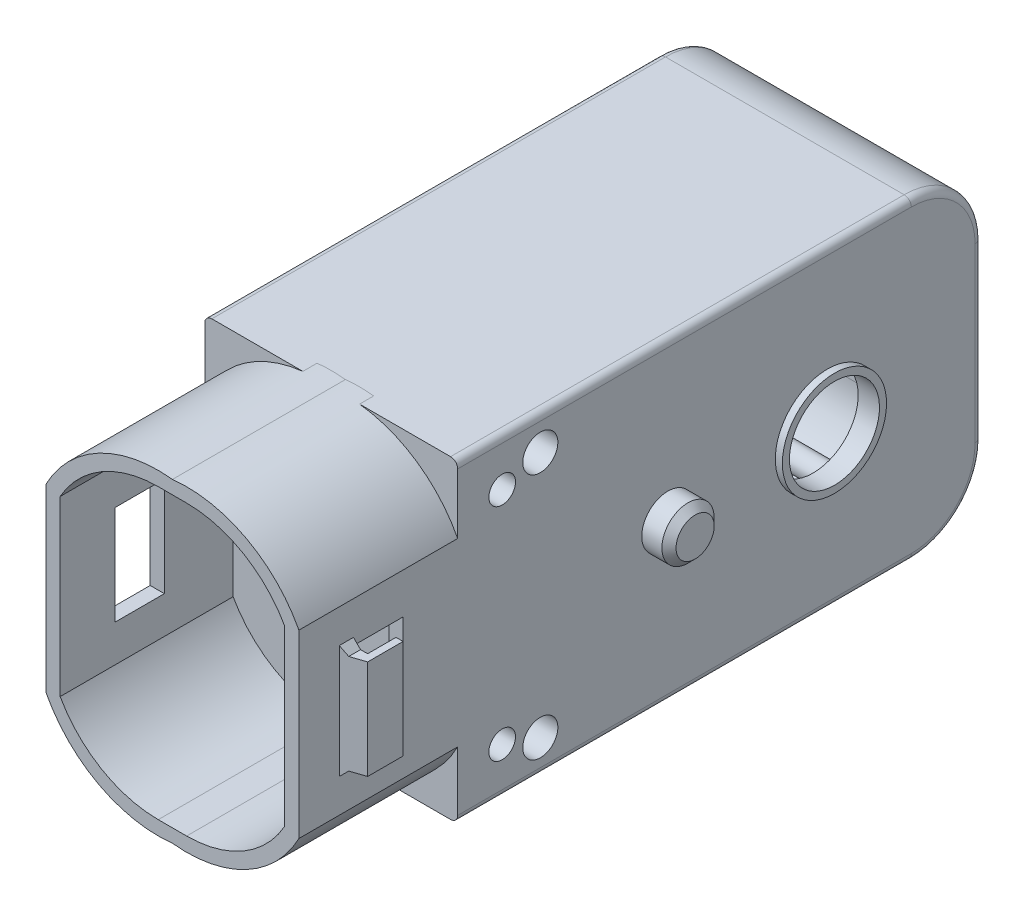
SolidWorks part; units mm, degrees
ref_plane "Front Plane" through (0, 0, 0) normal (0, 0, 1) x (1, 0, 0)
ref_plane "Top Plane" through (0, 0, 0) normal (0, 1, 0) x (1, 0, 0)
ref_plane "Right Plane" through (0, 0, 0) normal (1, 0, 0) x (0, 0, -1)
sketch "Sketch1" plane through (0, 0, 0) normal (0, 0, 1) x (1, 0, 0)
  line L0 (0, 11.115) -> (0, 10.1712)
  line L2 (-8.92, 6.365) -> (-8.92, -6.365)
  line L4 (-8.92, 6.365) -> (-8.92, -6.365) construction
  line L5 (55, 0) -> (-55, 0) construction
  line L7 (-7.92, 6.1126) -> (-7.92, -6.1126)
  line L8 (-1, 10.1712) -> (-1, -10.1712) construction
  line L9 (-1, 10.1712) -> (0, 10.1712)
  line L10 (-1, -10.1712) -> (0, -10.1712)
  line L11 (0, -10.1712) -> (0, -11.115)
  line L13 (0, 11.115) -> (0, -11.115) construction
  arc A0 (-8.92, 6.365) -> (0, 11.115) centre (-1, 2.2425) cw
  arc A1 (-8.92, -6.365) -> (0, -11.115) centre (-1, -2.2425) ccw
  arc A2 (-7.92, -6.1126) -> (-1, -10.1712) centre (-1, -2.2425) ccw
  arc A3 (-7.92, 6.1126) -> (-1, 10.1712) centre (-1, 2.2425) cw
  dimension "D1" = 22.23
  dimension "D2" = 12.73
  dimension "D3" = 1
extrude "Boss-Extrude1" add sketch "Sketch1" along normal blind 11.2
sketch "Sketch2" plane through (0, 0, 0) normal (0, 0, -1) x (-1, 0, 0)
  line L0 (0, -10.1712) -> (1, -10.1712) construction
  line L1 (2, 11.115) -> (8.92, 11.115)
  line L2 (0, 11.115) -> (0, 10.1712)
  line L3 (2.4484, -11.0529) -> (8.92, -11.0529)
  line L4 (8.92, 11.115) -> (8.92, -11.0529)
  line L5 (7.92, -6.1126) -> (7.92, 6.1126) construction
  line L6 (1, 10.1712) -> (0, 10.1712) construction
  line L7 (0, -10.1712) -> (1, -10.1712)
  line L8 (7.92, -6.1126) -> (7.92, 6.1126)
  line L9 (1, 10.1712) -> (0, 10.1712)
  line L10 (0, -10.1712) -> (0, -11.115)
  line L11 (8.92, 6.365) -> (8.92, -6.365) construction
  arc A0 (8.92, 6.365) -> (0, 11.115) centre (1, 2.2425) ccw construction
  arc A1 (2, 11.115) -> (0, 11.115) centre (1, 2.2425) ccw
  arc A2 (0, -11.115) -> (8.92, -6.365) centre (1, -2.2425) ccw construction
  arc A3 (0, -11.115) -> (2.4484, -11.0529) centre (1, -2.2425) ccw
  arc A4 (1, -10.1712) -> (7.92, -6.1126) centre (1, -2.2425) ccw construction
  arc A5 (7.92, 6.1126) -> (1, 10.1712) centre (1, 2.2425) ccw construction
  arc A6 (1, -10.1712) -> (7.92, -6.1126) centre (1, -2.2425) ccw
  arc A7 (7.92, 6.1126) -> (1, 10.1712) centre (1, 2.2425) ccw
extrude "Boss-Extrude2" add sketch "Sketch2" along normal blind 1
sketch "Sketch4" plane through (0, 0, -1) normal (0, 0, -1) x (-1, 0, 0)
  line L0 (0, -10.1712) -> (0, -11.115) construction
  line L1 (8.92, 11.115) -> (0, 11.115)
  line L2 (8.92, 11.115) -> (8.92, -11.0529)
  line L3 (8.92, -11.0529) -> (0, -11.0529)
  line L4 (0, 11.115) -> (0, 10.115)
  line L5 (2.4484, -11.0529) -> (8.92, -11.0529) construction
  line L6 (7.92, 10.115) -> (7.92, -10.0529)
  line L7 (7.92, -10.0529) -> (1, -10.0529)
  line L9 (7.92, 10.115) -> (1, 10.115)
  line L10 (1, 10.115) -> (0, 10.115)
  line L11 (1, -10.0529) -> (0, -10.0529)
  line L12 (0, -10.0529) -> (0, -11.0529)
  line L13 (1, 10.115) -> (1, -10.0529) construction
  line L15 (0, 11.115) -> (0, -11.0529) construction
  dimension "D1" = 1
extrude "Boss-Extrude4" add sketch "Sketch4" along normal blind 36
sketch "Sketch5" plane through (0, 0, -37) normal (0, 0, -1) x (-1, 0, 0)
  line L1 (0, 11.115) -> (8.92, 11.115)
  line L2 (0, 11.115) -> (0, -11.0529)
  line L3 (0, -11.0529) -> (8.92, -11.0529)
  line L4 (8.92, 11.115) -> (8.92, -11.0529)
extrude "Boss-Extrude6" add sketch "Sketch5" against normal blind 2
fillet "Fillet2" radius 5 4 edges at (-3.96, -10.0529, -35) (-3.96, 10.115, -35) (-4.46, -11.0529, -37) (-4.46, 11.115, -37)
sketch "Sketch6" plane through (0, 0, -37) normal (0, 0, -1) x (-1, 0, 0)
  line L0 (0, 0) -> (1.4, 0) construction
  line L1 (0, 6.115) -> (0, -6.0529) construction
  line L2 (1.4, -2.5) -> (0, -2.5)
  line L3 (1.4, -2.5) -> (1.4, 2.5)
  line L4 (1.4, 2.5) -> (0, 2.5)
  line L5 (0, -2.5) -> (0, 2.5)
  line L6 (1.4, -2.5) -> (0, 2.5) construction
  line L7 (1.4, 2.5) -> (0, -2.5) construction
  point P3 (0.7, 0)
  dimension "D1" = 1.4
  dimension "D2" = 5
extrude "Boss-Extrude7" add sketch "Sketch6" along normal blind 4.8
sketch "Sketch7" plane through (-1.4, 0, 0) normal (-1, 0, 0) x (0, 0, 1)
  line L0 (-39.4, 2.5) -> (-39.4, -2.5) construction
  line L1 (-41.8, 2.5) -> (-37, 2.5) construction
  line L2 (-41.8, -2.5) -> (-37, -2.5) construction
  line L3 (-37, -2.5) -> (-37, 2.5) construction
  circle A0 centre (-39.4, 0) radius 1.38
  dimension "D1" = 2.76
extrude "Cut-Extrude1" cut sketch "Sketch7" against normal blind 4.8
sketch "Sketch8" plane through (-8.92, 0, 0) normal (-1, 0, 0) x (0, 0, 1)
  line L0 (-37, 0) -> (-26.08, 0) construction
  line L1 (-37, -2.5) -> (-37, 2.5) construction
  circle A0 centre (-26.08, 0) radius 3.675
  circle A2 centre (-26.08, 0) radius 3.175
  dimension "D2" = 7.35
  dimension "D3" = 0.5
  dimension "D1" = 10.92
extrude "Boss-Extrude8" add sketch "Sketch8" along normal blind 0.5
sketch "Sketch9" plane through (-8.92, 0, 0) normal (-1, 0, 0) x (0, 0, 1)
  circle A1 centre (-26.08, 0) radius 3.175
  circle A2 centre (-26.08, 0) radius 3.175
  dimension "D1" = 0
extrude "Cut-Extrude2" cut sketch "Sketch9" against normal blind 7.5
chamfer "Chamfer1" distance 1 angle 45 2 edges at (-0.7, -2.5, -37) (-0.7, 2.5, -37)
sketch "Sketch10" plane through (-8.92, 0, 0) normal (-1, 0, 0) x (0, 0, 1)
  line L0 (-26.08, 0) -> (-14.83, 0) construction
  circle A0 centre (-14.83, 0) radius 1.845
  dimension "D2" = 3.69
  dimension "D1" = 11.25
extrude "Boss-Extrude9" add sketch "Sketch10" along normal blind 1.92
chamfer "Chamfer2" distance 0.5 angle 45 1 edges at (-10.84, 0, -12.985)
sketch "Sketch11" plane through (-8.92, 0, 0) normal (-1, 0, 0) x (0, 0, 1)
  line L0 (-14.83, 0) -> (-5.83, 0) construction
  line L1 (-5.83, 8.71) -> (-5.83, -8.71) construction
  line L2 (-37, -6.0529) -> (-37, 6.115) construction
  circle A0 centre (-5.83, 8.71) radius 1.5
  circle A1 centre (-5.83, -8.71) radius 1.5
  dimension "D4" = 3
  dimension "D1" = 31.17
  dimension "D2" = 17.42
extrude "Cut-Extrude3" cut sketch "Sketch11" against normal blind 1.92
sketch "Sketch12" plane through (-8.92, 0, 0) normal (-1, 0, 0) x (0, 0, 1)
  line L0 (4.906, 0) -> (-4.906, 0) construction
  circle A0 centre (-3.14, 7.7815) radius 1.15
  circle A1 centre (-3.14, -7.7815) radius 1.15
  dimension "D1" = 2.3
extrude "Cut-Extrude4" cut sketch "Sketch12" against normal blind 1.92
ref_plane "Plane1" through (0, 0, -1) normal (0, 0, -1) x (-1, 0, 0)
sketch "Sketch13" plane through (0, 0, -1) normal (0, 0, -1) x (-1, 0, 0)
  line L0 (0, -10.1712) -> (1, -10.1712) construction
  line L1 (7.92, 10.115) -> (0, 10.115)
  line L2 (7.92, 10.115) -> (7.92, -10.1712)
  line L3 (7.92, -10.1712) -> (0.5, -10.1712)
  line L4 (0, 10.115) -> (0, 2.5)
  line L6 (0, 10.115) -> (0, 5.115) construction
  line L7 (4.906, 0) -> (-4.906, 0) construction
  line L8 (0, -10.115) -> (0, -2.5)
  line L9 (0.5, -10.1712) -> (0, -10.1712)
  line L10 (0, -10.1712) -> (0, -10.115)
  arc A0 (0, -2.5) -> (0, 2.5) centre (0, 0) ccw
  dimension "D1" = 5
extrude "Boss-Extrude13" add sketch "Sketch13" along normal blind 0.5
sketch "Sketch14" plane through (-8.92, 0, 0) normal (-1, 0, 0) x (0, 0, 1)
  line L0 (5.6, 6.365) -> (5.6, -6.365) construction
  line L1 (11.2, 6.365) -> (0, 6.365) construction
  line L2 (11.2, -6.365) -> (0, -6.365) construction
  line L4 (7.35, -3.5) -> (3.85, -3.5)
  line L5 (7.35, -3.5) -> (7.35, 3.5)
  line L6 (7.35, 3.5) -> (3.85, 3.5)
  line L7 (3.85, -3.5) -> (3.85, 3.5)
  line L8 (7.35, -3.5) -> (3.85, 3.5) construction
  line L9 (7.35, 3.5) -> (3.85, -3.5) construction
  point P6 (5.6, 0)
  dimension "D1" = 7
  dimension "D2" = 3.5
extrude "Cut-Extrude6" cut sketch "Sketch14" against normal blind 5.5
sketch "Sketch15" plane through (0, 3.5, 0) normal (0, -1, 0) x (1, 0, 0)
  line L0 (-8.92, 7.35) -> (-10.42, 7.35)
  line L1 (-10.42, 7.85) -> (-8.92, 8.35)
  line L2 (-8.92, 11.2) -> (-8.92, 0) construction
  line L3 (-8.92, 8.35) -> (-8.92, 7.35)
  line L4 (-10.42, 7.85) -> (-10.42, 7.35)
  dimension "D1" = 1.5
  dimension "D2" = 0.5
  dimension "D3" = 1
extrude "Boss-Extrude14" add sketch "Sketch15" along normal blind 7
sketch "Sketch16" plane through (0, 0, 7.35) normal (0, 0, -1) x (-1, 0, 0)
  line L0 (10.42, -3.5) -> (8.92, -3.5) construction
  line L1 (10.42, 3.5) -> (9.92, 3.5)
  line L2 (10.42, 3.5) -> (10.42, -3.5)
  line L3 (10.42, -3.5) -> (9.92, -3.5)
  line L4 (9.92, 3.5) -> (9.92, -3.5)
extrude "Boss-Extrude16" add sketch "Sketch16" along normal blind 2
chamfer "Chamfer3" distance 0.5 angle 45 2 edges at (-8.92, -3.5, 7.85) (-8.92, 3.5, 7.85)
sketch "Sketch20" plane through (-7.92, 0, 0) normal (1, 0, 0) x (0, 0, -1)
  line L0 (16.175, 0) -> (16.675, 0) construction
  circle A3 centre (14.83, 0) radius 1.345 construction
  circle A4 centre (14.83, 0) radius 1.845 construction
  circle A5 centre (16.425, 0) radius 0.5
extrude "Boss-Extrude19" add sketch "Sketch20" along normal blind 15
sketch "Sketch21" plane through (-7.92, 0, 0) normal (1, 0, 0) x (0, 0, -1)
  line L0 (4.906, 0) -> (-4.906, 0) construction
  circle A0 centre (5.83, 8.71) radius 1.5
  circle A1 centre (3.14, 7.7815) radius 1.15
  circle A2 centre (5.83, 8.71) radius 1.238
  circle A3 centre (3.14, 7.7815) radius 0.9401
  circle A4 centre (3.14, -7.7815) radius 0.9401
  circle A5 centre (5.83, -8.71) radius 1.238
  circle A6 centre (3.14, -7.7815) radius 1.15
  circle A7 centre (5.83, -8.71) radius 1.5
  point P16 (5.83, -8.71)
extrude "Boss-Extrude23" add sketch "Sketch21" against normal blind 1
extrude "Boss-Extrude24" add sketch "Sketch21<2>" along normal blind 8
sketch "Sketch21<2>" plane through (-7.92, 0, 0) normal (1, 0, 0) x (0, 0, -1) same geometry as "Sketch21"
sketch "Sketch22" plane through (-7.92, 0, 0) normal (1, 0, 0) x (0, 0, -1)
  line L0 (4.906, 0) -> (-4.906, 0) construction
  circle A0 centre (17.5264, 9.0814) radius 0.5
  circle A1 centre (17.5264, 9.0814) radius 0.8
  circle A2 centre (31.7978, 8.5923) radius 0.5
  circle A3 centre (31.7978, 8.5923) radius 0.8
  circle A4 centre (31.7978, -8.5923) radius 0.8
  circle A5 centre (31.7978, -8.5923) radius 0.5
  circle A6 centre (17.5264, -9.0814) radius 0.8
  circle A7 centre (17.5264, -9.0814) radius 0.5
extrude "Boss-Extrude25" add sketch "Sketch22" along normal blind 8
mirror "Mirror7" about plane through (0, 0, 0) normal (1, 0, 0) of bodies 131
fillet "Fillet4" radius 0.5 10 edges at (-8.92, -11.0529, -16) (-8.92, -9.5885, -35.5355) (-8.92, 0.031, -37) (-8.92, 9.6505, -35.5355) (8.92, -11.0529, -16) (8.92, -9.5885, -35.5355) (8.92, 0.031, -37) (8.92, 9.6505, -35.5355) (-8.92, 11.115, -16) (8.92, 11.115, -16)
